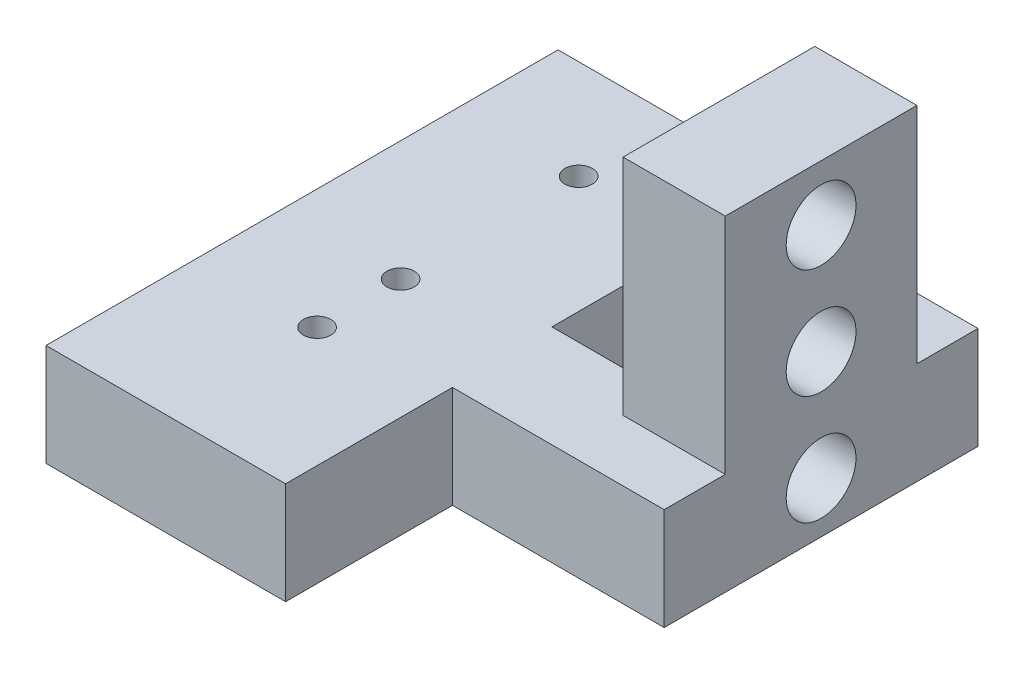
SolidWorks part; units mm, degrees
ref_plane "Front Plane" through (0, 0, 0) normal (0, 0, 1) x (1, 0, 0)
ref_plane "Top Plane" through (0, 0, 0) normal (0, 1, 0) x (1, 0, 0)
ref_plane "Right Plane" through (0, 0, 0) normal (1, 0, 0) x (0, 0, -1)
sketch "Sketch1" plane through (0, 0, 0) normal (0, 1, 0) x (1, 0, 0)
  line L0 (0, 95.561) -> (0, -103.6026) construction
  line L1 (-120.0879, 0) -> (122.2323, 0) construction
  line B0 (0, 24.3119) -> (0, -27.7936) construction
  line B1 (-27.8941, 0) -> (23.9754, 0) construction
  line B2 (8.75, 11.46) -> (24.21, 11.46)
  line B3 (8.55, 4) -> (16.75, 4)
  line B4 (8.55, 4) -> (8.55, -4)
  line B5 (8.55, -4) -> (16.75, -4)
  line B6 (16.75, 4) -> (16.75, -4)
  line B7 (8.55, 4) -> (16.75, -4) construction
  line B8 (8.55, -4) -> (16.75, 4) construction
  line B9 (-8.75, 13.75) -> (8.75, 13.75)
  line B10 (-8.75, 13.75) -> (-8.75, -23.65)
  line B11 (-8.75, -23.65) -> (8.75, -23.65)
  line B12 (8.75, 13.75) -> (8.75, 11.46)
  line B13 (-8.75, 13.75) -> (8.75, -23.65) construction
  line B14 (-8.75, -23.65) -> (8.75, 13.75) construction
  line B15 (24.21, 11.46) -> (24.21, -11.46)
  line B16 (8.75, -11.46) -> (24.21, -11.46)
  line B17 (8.75, -11.46) -> (8.75, -23.65)
  dimension "D1" = 0
  dimension "D2" = 0
sketch_block_instance "Block3-1"
sketch_block "Block3" parameters "D1"=8.2, "D2"=8, "D3"=12.65, "D4"=7.46, "D5"=7.46
extrude "Boss-Extrude1" add sketch "Sketch1" along normal blind 7.46
sketch "Sketch3" plane through (0, 7.46, 0) normal (0, 1, 0) x (1, 0, 0)
  line L0 (16.75, 0) -> (24.21, 0) construction
  line L1 (16.75, -4) -> (16.75, 4) construction
  line L2 (24.21, -11.46) -> (24.21, 11.46) construction
  line L3 (16.75, 7) -> (24.21, 7)
  line L4 (16.75, -7) -> (24.21, -7)
  line L5 (16.75, -7) -> (16.75, -4)
  line L6 (16.75, 4) -> (16.75, 7)
  line L7 (16.75, -4) -> (16.75, 4)
  line L8 (24.21, -7) -> (24.21, 7)
  dimension "D1" = 7
extrude "Boss-Extrude2" add sketch "Sketch3" along normal blind 16.34
sketch "Sketch4" plane through (16.75, 0, 0) normal (-1, 0, 0) x (0, 0, 1)
  line L0 (-4, 3.73) -> (4, 3.73) construction
  line L1 (-4, 7.46) -> (-4, 0) construction
  line L2 (4, 7.46) -> (4, 0) construction
  line L3 (0, 0) -> (0, 23.8) construction
  line L4 (4, 0) -> (-4, 0) construction
  line L5 (-7, 23.8) -> (7, 23.8) construction
  circle A0 centre (0, 3.73) radius 2.55
  circle A1 centre (0, 11.73) radius 2.55
  circle A2 centre (0, 19.73) radius 2.55
  point P14 (0, 0)
  point P15 (0, 0)
  point P20 (0, 0)
  point P21 (0, 0)
  point P22 (0, 0)
  point P23 (0, 0)
  point P24 (0, 0)
  point P25 (0, 0)
  point P26 (0, 0)
  dimension "D1" = 5.1
  dimension "D3" = 8
  dimension "D2" = 3
extrude "Cut-Extrude1" cut sketch "Sketch4" against normal through all
sketch "Sketch5" plane through (0, 0, 0) normal (0, -1, 0) x (1, 0, 0)
  line L0 (8.55, 0) -> (-8.75, 0) construction
  line L1 (8.55, -4) -> (8.55, 4) construction
  line L2 (-8.75, -13.75) -> (-8.75, 23.65) construction
  line L3 (0, -13.75) -> (0, 23.65) construction
  line L4 (8.75, -13.75) -> (-8.75, -13.75) construction
  line L5 (-8.75, 23.65) -> (8.75, 23.65) construction
  line B0 (4.9, 0) -> (-4.9, 0) construction
  line B1 (0, 18) -> (0, -18) construction
  line B2 (4.9, 14.75) -> (-5.1593, 14.75) construction
  line B3 (4.9, -14.75) -> (-5.1593, -14.75) construction
  line B4 (-2.114, 14.9661) -> (-3.6062, 0.3686)
  line B5 (-3.6062, -0.3686) -> (-2.114, -14.9661)
  line B6 (2.114, -14.9661) -> (3.6062, -0.3686)
  line B7 (2.114, 14.9661) -> (3.6062, 0.3686)
  arc B8 (2.114, 14.9661) -> (-2.114, 14.9661) centre (0, 14.75) ccw
  arc B9 (-3.6062, 0.3686) -> (-3.6062, -0.3686) centre (0, 0) ccw
  arc B10 (2.114, -14.9661) -> (-2.114, -14.9661) centre (0, -14.75) cw
  arc B11 (3.6062, -0.3686) -> (3.6062, 0.3686) centre (0, 0) ccw
  dimension "D2" = 0
  dimension "D1" = 0
sketch_block_instance "Block5-1"
sketch_block "Block5" parameters "D2"=4.25, "D3"=7.25, "D1"=14.75
extrude "Cut-Extrude2" cut sketch "Sketch5" against normal blind 1.1
sketch "Sketch6" plane through (0, 1.1, 0) normal (0, -1, 0) x (1, 0, 0)
  line L0 (0, 0) -> (-3.625, 0) construction
  line L1 (0, 0) -> (0, 16.875) construction
  line L2 (0, 6.5) -> (1.6708, 6.5) construction
  line L3 (0, 12.6) -> (1.6708, 12.6) construction
  line L4 (0, 0) -> (0, -13.75) construction
  line L5 (-2.2383, -13.75) -> (2.2383, -13.75) construction
  line L6 (0, -6.5) -> (1.6708, -6.5) construction
  arc A0 (-3.6062, 0.3686) -> (-3.6062, -0.3686) centre (0, 0) ccw construction
  arc A1 (2.114, 14.9661) -> (-2.114, 14.9661) centre (0, 14.75) ccw construction
  circle A2 centre (0, 12.6) radius 1
  circle A3 centre (0, 6.5) radius 1
  circle A4 centre (0, -6.5) radius 1
  dimension "D3" = 2
  dimension "D4" = 2
  dimension "D7" = 2
  dimension "D1" = 6.5
  dimension "D2" = 12.6
  dimension "D5" = 6.5
extrude "Cut-Extrude4" cut sketch "Sketch6" against normal up to next
